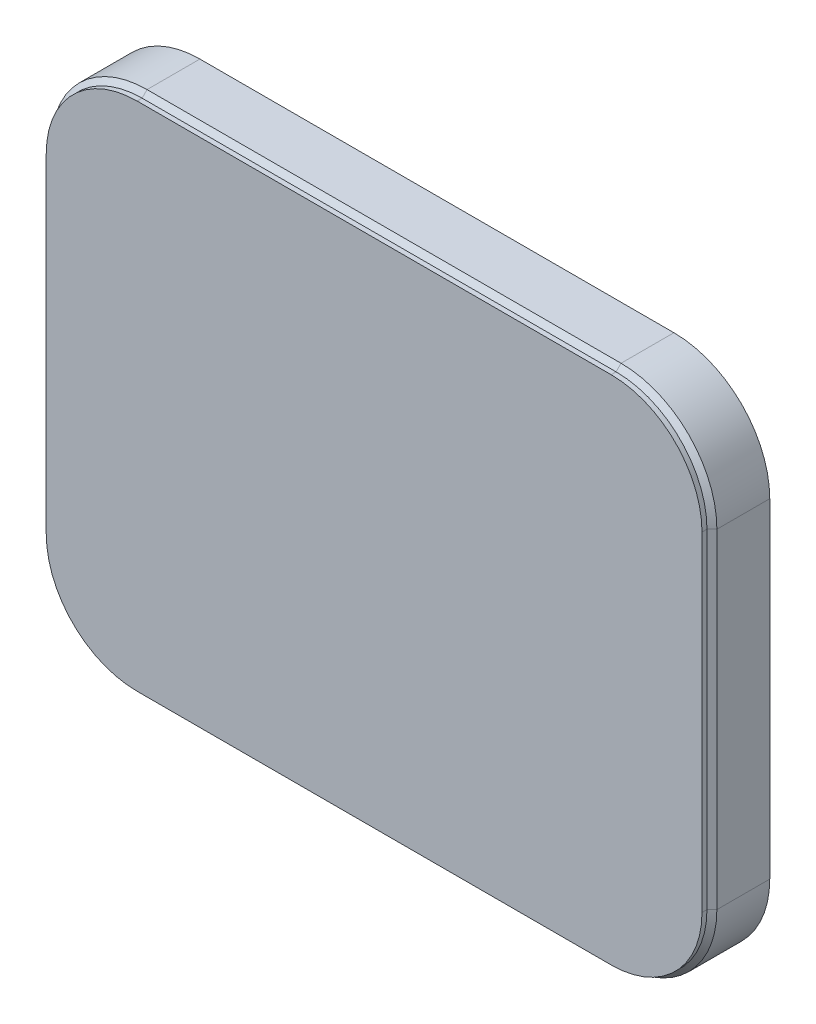
SolidWorks part; units mm, degrees
ref_plane "Front Plane" through (0, 0, 0) normal (0, 0, 1) x (1, 0, 0)
ref_plane "Top Plane" through (0, 0, 0) normal (0, 1, 0) x (1, 0, 0)
ref_plane "Right Plane" through (0, 0, 0) normal (1, 0, 0) x (0, 0, -1)
sketch "BasketRing" plane through (0, 0, 0) normal (0, 0, 1) x (1, 0, 0)
  line L1 (44, 0) -> (273.5, 0)
  line L2 (0, 44) -> (0, 203.5)
  line L3 (44, 247.5) -> (273.5, 247.5)
  line L4 (317.5, 44) -> (317.5, 203.5)
  line L5 (0, 0) -> (317.5, 247.5) construction
  line L6 (0, 247.5) -> (317.5, 0) construction
  arc A0 (273.5, 0) -> (317.5, 44) centre (273.5, 44) ccw
  arc A1 (317.5, 203.5) -> (273.5, 247.5) centre (273.5, 203.5) ccw
  arc A2 (0, 203.5) -> (44, 247.5) centre (44, 203.5) cw
  arc A3 (44, 0) -> (0, 44) centre (44, 44) cw
  point P4 (158.75, 123.75)
  dimension "D3" = 44
  dimension "D1" = 317.5
  dimension "D2" = 247.5
ref_plane "Plane1" through (44, 0, 0) normal (1, 0, 0) x (0, 0, -1)
ref_plane "Plane3" through (158.75, 0, 0) normal (1, 0, 0) x (0, 0, -1)
sketch "ShapeOf Edge" plane through (44, 0, 0) normal (1, 0, 0) x (0, 0, -1)
  line L32 (0, 0) -> (2.4, 0)
  line L33 (2.4, 0) -> (4.8, -2.4)
  line L34 (0, 0) -> (0, 7)
  line L35 (0, 44) -> (0, 0) construction
  line L36 (0, 7) -> (2.4, 7)
  line L38 (5.7941, 0) -> (30.4, 0)
  line L39 (30.4, 0) -> (30.4, -2.4)
  line L40 (30.4, -2.4) -> (4.8, -2.4)
  line L43 (2.4, 7) -> (2.4, 3.3941)
  line L44 (2.4, 3.3941) -> (5.7941, 0)
  dimension "D1" = 7
  dimension "D2" = 2.4
  dimension "D5" = 135
  dimension "D6" = 2.4
  dimension "D10" = 2.4
  dimension "D3" = 2.4
  dimension "D4" = 25.6
sweep "Sweep2" add profiles "ShapeOf Edge" path "BasketRing"
sketch "Sketch1" plane through (0, 0, 0) normal (0, 0, 1) x (1, 0, 0)
  line L0 (44, 240.5) -> (273.5, 240.5) construction
  line L1 (310.5, 203.5) -> (310.5, 44) construction
  line L2 (273.5, 7) -> (44, 7) construction
  line L3 (7, 44) -> (7, 203.5) construction
  line L4 (44, 240.5) -> (273.5, 240.5)
  line L5 (310.5, 203.5) -> (310.5, 44)
  line L6 (273.5, 7) -> (44, 7)
  line L7 (7, 44) -> (7, 203.5)
  arc A0 (44, 240.5) -> (7, 203.5) centre (44, 203.5) ccw construction
  arc A1 (310.5, 203.5) -> (273.5, 240.5) centre (273.5, 203.5) ccw construction
  arc A2 (273.5, 7) -> (310.5, 44) centre (273.5, 44) ccw construction
  arc A3 (7, 44) -> (44, 7) centre (44, 44) ccw construction
  arc A4 (44, 240.5) -> (7, 203.5) centre (44, 203.5) ccw
  arc A5 (310.5, 203.5) -> (273.5, 240.5) centre (273.5, 203.5) ccw
  arc A6 (273.5, 7) -> (310.5, 44) centre (273.5, 44) ccw
  arc A7 (7, 44) -> (44, 7) centre (44, 44) ccw
extrude "Boss-Extrude1" add sketch "Sketch1" against normal up to surface (2.4 mm away) up to face at (5.1971, 123.75, -2.4)
sketch "Sketch2" plane through (0, 0, -2.4) normal (0, 0, -1) x (-1, 0, 0)
  line L0 (-314.1059, 123.75) -> (-3.3941, 123.75) construction
  line L1 (-314.1059, 203.5) -> (-314.1059, 44) construction
  line L2 (-3.3941, 44) -> (-3.3941, 203.5) construction
  line L3 (-158.75, 244.1059) -> (-158.75, 3.3941) construction
  line L4 (-44, 244.1059) -> (-273.5, 244.1059) construction
  line L5 (-273.5, 3.3941) -> (-44, 3.3941) construction
  circle A0 centre (-158.75, 123.75) radius 32.5
  dimension "D1" = 65
extrude "Boss-Extrude2" add sketch "Sketch2" along normal blind 10
sketch "Sketch3" plane through (0, 0, -12.4) normal (0, 0, -1) x (-1, 0, 0)
  circle A0 centre (-158.75, 123.75) radius 29
  dimension "D1" = 58
extrude "Boss-Extrude3" add sketch "Sketch3" along normal blind 12 draft 22.5
equation "\"height\"= 28 - 2.4"
equation "\"D4@ShapeOf Edge\"=\"height\""
